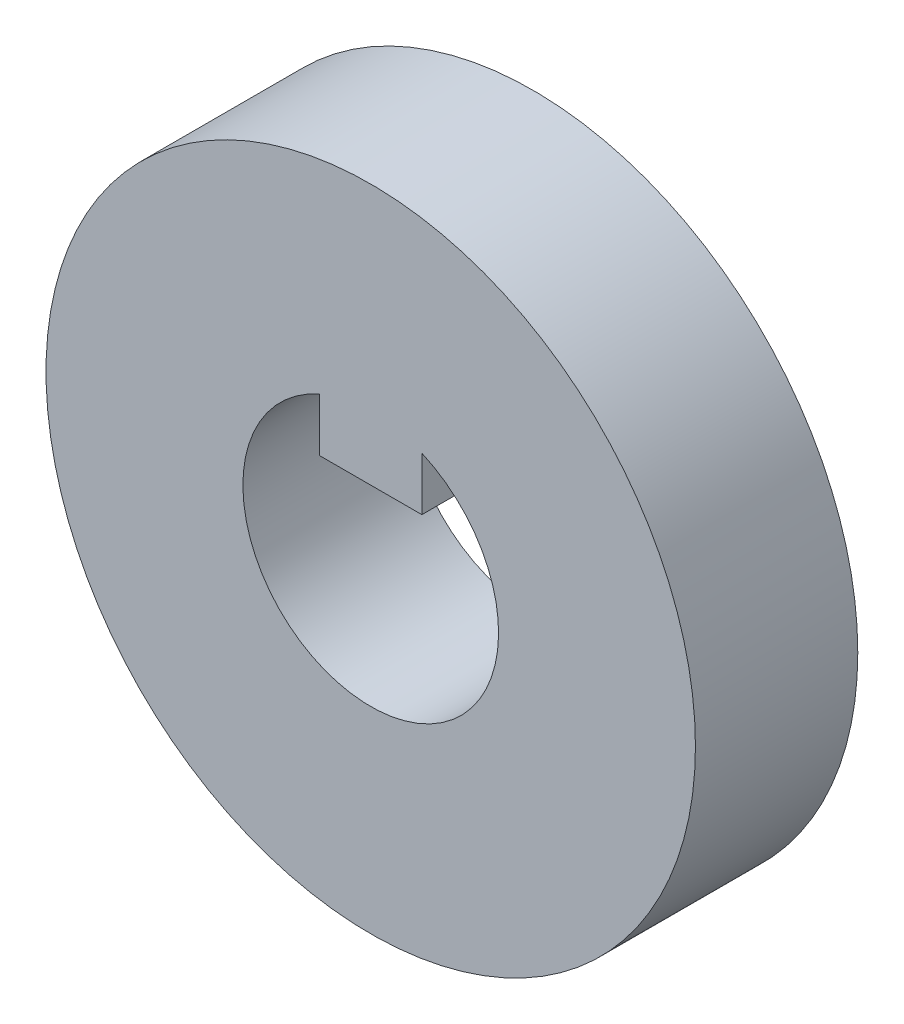
SolidWorks part; units mm, degrees
ref_plane "Front Plane" through (0, 0, 0) normal (0, 0, 1) x (1, 0, 0)
ref_plane "Top Plane" through (0, 0, 0) normal (0, 1, 0) x (1, 0, 0)
ref_plane "Right Plane" through (0, 0, 0) normal (1, 0, 0) x (0, 0, -1)
sketch "Sketch1" plane through (0, 0, 0) normal (0, 0, 1) x (1, 0, 0)
  line L1 (4, 15) -> (-4, 15)
  line L2 (4, 15) -> (4, 5)
  line L3 (4, 5) -> (-4, 5)
  line L4 (-4, 15) -> (-4, 5)
  line L5 (4, 15) -> (-4, 5) construction
  line L6 (4, 5) -> (-4, 15) construction
  circle A0 centre (0, 0) radius 25.4
  circle A1 centre (0, 0) radius 10
  point P4 (0, 10)
  dimension "D1" = 50.8
  dimension "D2" = 20
  dimension "D3" = 8
  dimension "D4" = 10
extrude "Boss-Extrude1" add sketch "Sketch1" along normal blind 12.7 contours A0 A1 L4 L1 L2 | L2 L1 L4 L3 region at (-24.6816, 0, 0)
equation "\"shaftDiam\" = 20mm"
equation "\"keyW\" = 8mm"
equation "\"keyL\" = 10mm"
equation "\"clearance\" = 1mm"
equation "\"shafDiam_\"= \"shaftDiam\""
equation "\"keyL_\"= \"keyL\""
equation "\"keyW_\"= \"keyW\""
equation "\"D3@Sketch1\"=\"keyW_\""
equation "\"D4@Sketch1\"=\"keyL_\""
equation "\"D2@Sketch1\"=\"shafDiam_\""
